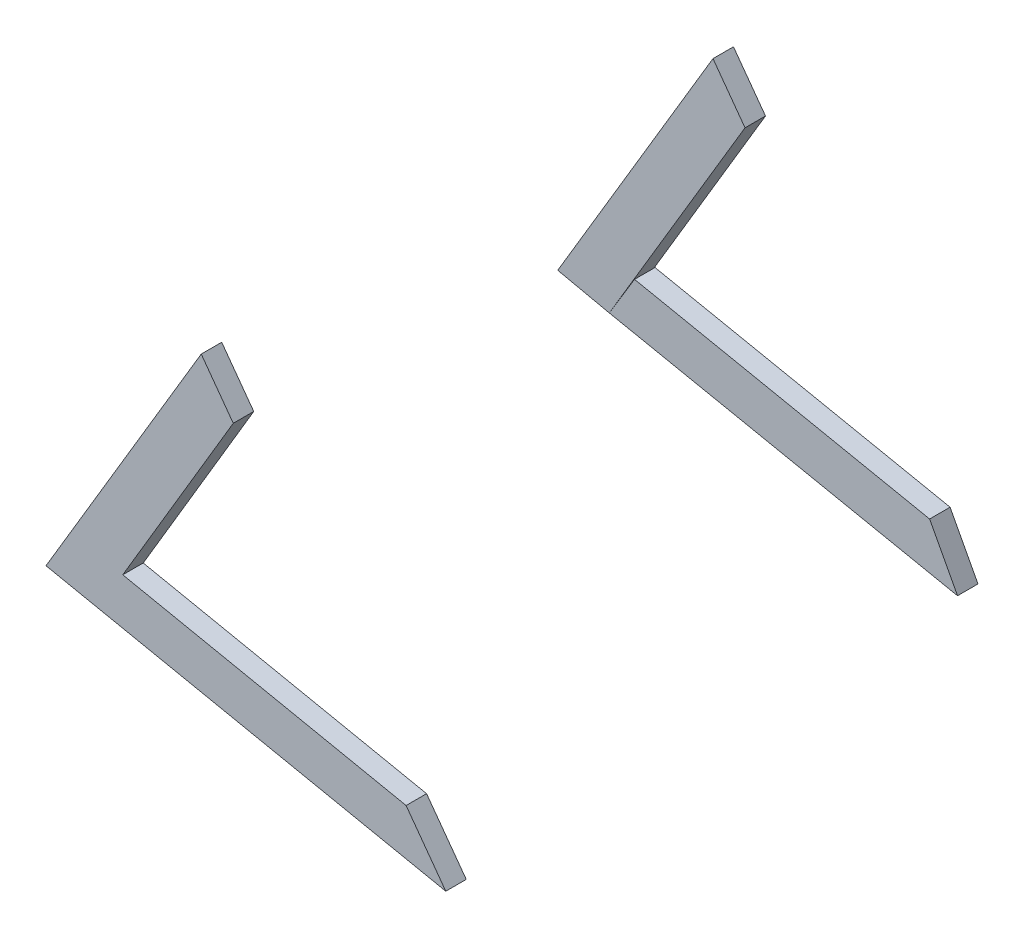
SolidWorks part; units mm, degrees
ref_plane "Front Plane" through (0, 0, 0) normal (0, 0, 1) x (1, 0, 0)
ref_plane "Top Plane" through (0, 0, 0) normal (0, 1, 0) x (1, 0, 0)
ref_plane "Right Plane" through (0, 0, 0) normal (1, 0, 0) x (0, 0, -1)
ref_plane "Plane1"
sketch "Sketch1" plane through (1143.7783, 851.9673, -406.3915) normal (0, 0, -1) x (-0.8081, -0.5891, 0)
  line L0 (1567.246, 44.5125) -> (1511.4503, 67.8864)
  line L1 (1511.4503, 67.8864) -> (1259.4205, -207.9841)
  line L2 (1259.4205, -207.9841) -> (1269.8194, -281.049)
  line L3 (1269.8194, -281.049) -> (1567.246, 44.5125)
extrude "Extrusion1" add sketch "Sketch1" against normal blind 25.4
ref_plane "Plane2"
sketch "Sketch2" plane through (1143.7783, 851.9673, -406.3915) normal (0, 0, -1) x (-0.8081, -0.5891, 0)
  line L0 (1264.3348, 241.5423) -> (1610.7303, 93.3818)
  line L1 (1610.7303, 93.3818) -> (1567.246, 44.5125)
  line L2 (1567.246, 44.5125) -> (1264.3348, 174.0739)
  line L3 (1264.3348, 174.0739) -> (1264.3348, 241.5423)
extrude "Extrusion3" add sketch "Sketch2" against normal blind 25.4
ref_plane "Plane3"
sketch "Sketch3" plane through (1129.2131, 527.0149, 254.0085) normal (0, 0, 1) x (0.8081, 0.5891, 0)
  line L0 (-1061.1348, 428.0739) -> (-1061.1348, 495.5423)
  line L1 (-1061.1348, 495.5423) -> (-1407.5303, 347.3818)
  line L2 (-1407.5303, 347.3818) -> (-1066.6194, -27.049)
  line L3 (-1066.6194, -27.049) -> (-1066.6194, 56.4973)
  line L4 (-1066.6194, 56.4973) -> (-1308.2503, 321.8864)
  line L5 (-1308.2503, 321.8864) -> (-1061.1348, 428.0739)
extrude "Extrusion4" add sketch "Sketch3" against normal blind 25.4
ref_plane "Plane4"
sketch "Sketch4" plane through (1143.7783, 851.9673, -380.9915) normal (0, 0, 1) x (0.8081, 0.5891, 0)
  line L0 (-1521.1481, 74.7883) -> (-1559.35, 115.3583)
  line L1 (-1559.35, 115.3583) -> (-1610.7303, 93.3818)
  line L2 (-1610.7303, 93.3818) -> (-1559.35, 38.8164)
  line L3 (-1559.35, 38.8164) -> (-1521.1481, 74.7883)
extrude "Extrusion5" add sketch "Sketch4" along normal blind 635 rebuild error yes
